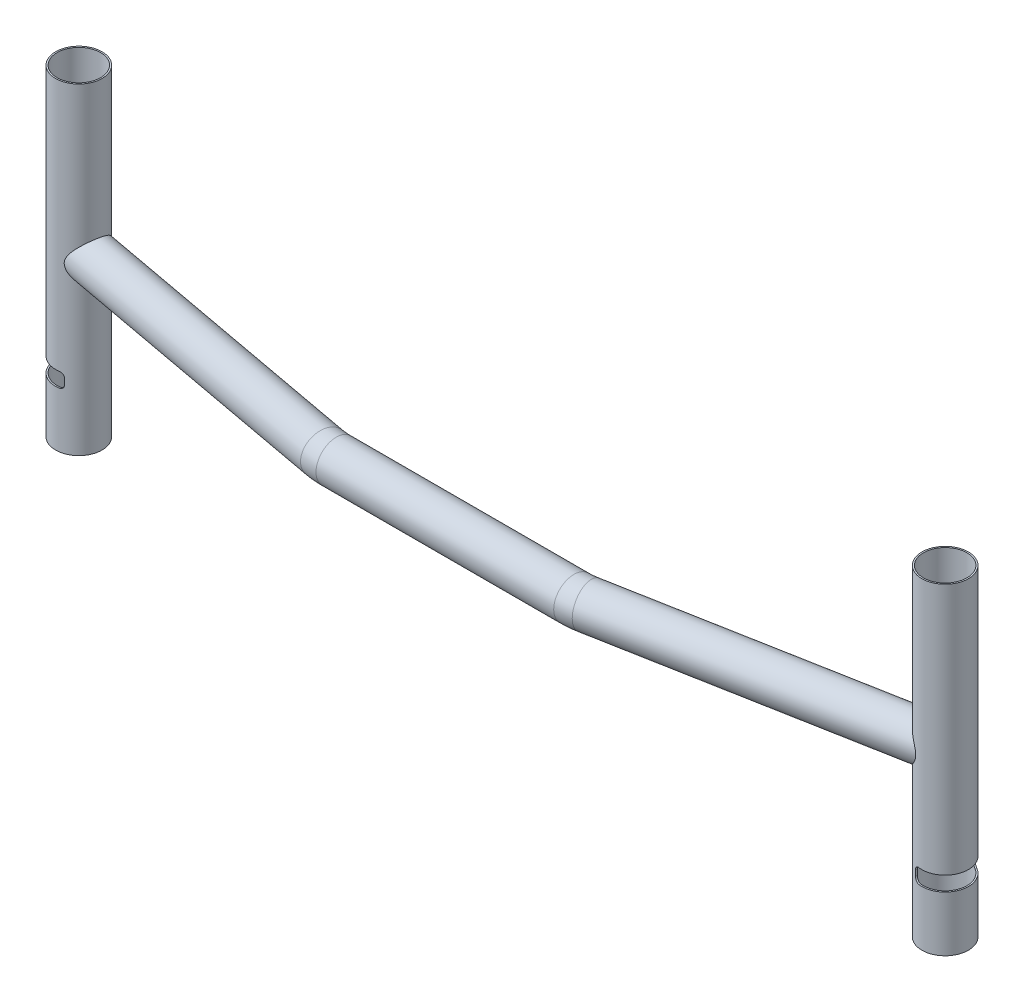
SolidWorks part; units mm, degrees
ref_plane "Front Plane" through (0, 0, 0) normal (0, 0, 1) x (1, 0, 0)
ref_plane "Top Plane" through (0, 0, 0) normal (0, 1, 0) x (1, 0, 0)
ref_plane "Right Plane" through (0, 0, 0) normal (1, 0, 0) x (0, 0, -1)
sketch "Sketch1" plane through (0, 0, 0) normal (0, 1, 0) x (1, 0, 0)
  line L0 (0, 0) -> (0, 107.988) construction
  line L1 (-65, 0) -> (65, 0)
  line L2 (72.269, 0.666) -> (231, 30)
  line L3 (-72.269, 0.666) -> (-231, 30)
  arc A0 (72.269, 0.666) -> (65, 0) centre (65, 40) cw
  arc A1 (-72.269, 0.666) -> (-65, 0) centre (-65, 40) ccw
  dimension "D2" = 40
  dimension "D1" = 231
  dimension "D3" = 65
  dimension "D4" = 30
ref_plane "Plane1" through (231, 0, -30) normal (0.9833, 0, -0.1817) x (-0.1817, 0, -0.9833)
sketch "Sketch2" plane through (231, 0, -30) normal (0.9833, 0, -0.1817) x (-0.1817, 0, -0.9833)
  line L0 (0.666, 0) -> (0, 0) construction
  circle A0 centre (0, 0) radius 11.1
  circle A1 centre (0, 0) radius 10.3
  dimension "D1" = 0.8
  dimension "D2" = 22.2
sweep "Sweep1" add profiles "Sketch2" path "Sketch1"
sketch "Sketch3" plane through (0, 0, 0) normal (0, 1, 0) x (1, 0, 0)
  line L0 (228.9828, 40.9152) -> (233.0172, 19.0848) construction
  line L1 (228.9828, 40.9152) -> (231, 30) construction
  line L2 (231, 30) -> (236.9001, 31.0904) construction
  circle A0 centre (236.9001, 31.0904) radius 12.7
  circle A1 centre (236.9001, 31.0904) radius 11.9
  dimension "D1" = 0.8
  dimension "D3" = 25.4
  dimension "D4" = 0.8
  dimension "D2" = 6
extrude "Boss-Extrude1" add sketch "Sketch3" along normal blind 85.8 and the other way blind 90.2
sketch "Sketch4" plane through (0, -90.2, 0) normal (0, -1, 0) x (1, 0, 0)
  circle A0 centre (236.9001, -31.0904) radius 11.9
extrude "Cut-Extrude1" cut sketch "Sketch4" against normal through all
sketch "Sketch5" plane through (231, 0, -30) normal (0.9833, 0, -0.1817) x (-0.1817, 0, -0.9833)
  circle A0 centre (-0.0149, 0) radius 10.7
  dimension "D1" = 21.4
extrude "Cut-Extrude2" cut sketch "Sketch5" against normal blind 88
sketch "Sketch6" plane through (0, 85.8, 0) normal (0, 1, 0) x (1, 0, 0)
  line L0 (236.9001, 31.0904) -> (72.269, 0.666)
  line L1 (70.2519, 11.5812) -> (74.2862, -10.2491) construction
  line L2 (236.9001, 31.0904) -> (240.8782, 42.3057)
  circle A0 centre (236.9001, 31.0904) radius 11.9 construction
  dimension "D1" = 60
ref_plane "Plane2" through (236.9001, 85.8, -31.0904) normal (0.3343, 0, -0.9425) x (-0.9425, 0, -0.3343)
sketch "Sketch7" plane through (236.9001, 85.8, -31.0904) normal (0.3343, 0, -0.9425) x (-0.9425, 0, -0.3343)
  line L0 (0, -176) -> (0, -141.8) construction
  line L1 (-12.7, -176) -> (12.7, -176) construction
  line L4 (-2.5, -137.8) -> (-12.7, -137.8)
  line L5 (-2.5, -145.8) -> (-12.7, -145.8)
  line L6 (-12.7, -137.8) -> (-12.7, -145.8)
  line L7 (0, -140.3) -> (0, -143.3)
  arc A0 (0, -140.3) -> (-2.5, -137.8) centre (-2.5, -140.3) ccw
  arc A1 (0, -143.3) -> (-2.5, -145.8) centre (-2.5, -143.3) cw
  dimension "D1" = 2.5
  dimension "D2" = 34.2
extrude "Cut-Extrude3" cut sketch "Sketch7" against normal blind 20 and the other way blind 20
mirror "Mirror1" about plane through (0, 0, 0) normal (1, 0, 0) of "Cut-Extrude1", "Boss-Extrude1", "Cut-Extrude3", "Cut-Extrude2"
sketch "Sketch8" plane through (0, 0, 0) normal (0, 1, 0) x (1, 0, 0)
  line L0 (72.269, 0.666) -> (216.9875, 26.5937) construction
  line L1 (70.2519, 11.5812) -> (74.2862, -10.2491) construction
  circle A0 centre (216.9875, 26.5937) radius 3
extrude "Cut-Extrude4" cut sketch "Sketch8" against normal up to next
ref_plane "Plane3" through (0, 0, -50) normal (0, 0, 1) x (1, 0, 0)
sketch "Sketch11" plane through (0, 0, -50) normal (0, 0, 1) x (1, 0, 0)
  line L0 (224.2001, -90.2) -> (249.6001, -90.2) construction
  line L1 (234.9001, -96.2) -> (238.9001, -96.2)
  line L2 (234.9001, -96.2) -> (234.9001, -84.2)
  line L3 (234.9001, -84.2) -> (238.9001, -84.2)
  line L4 (238.9001, -96.2) -> (238.9001, -84.2)
  line L5 (234.9001, -96.2) -> (238.9001, -84.2) construction
  line L6 (234.9001, -84.2) -> (238.9001, -96.2) construction
  point P0 (236.9001, -90.2)
  dimension "D1" = 12
  dimension "D2" = 4
extrude "Cut-Extrude6" cut sketch "Sketch11" along normal up to next
mirror "Mirror2" about plane through (0, 0, 0) normal (1, 0, 0) of "Cut-Extrude6"
